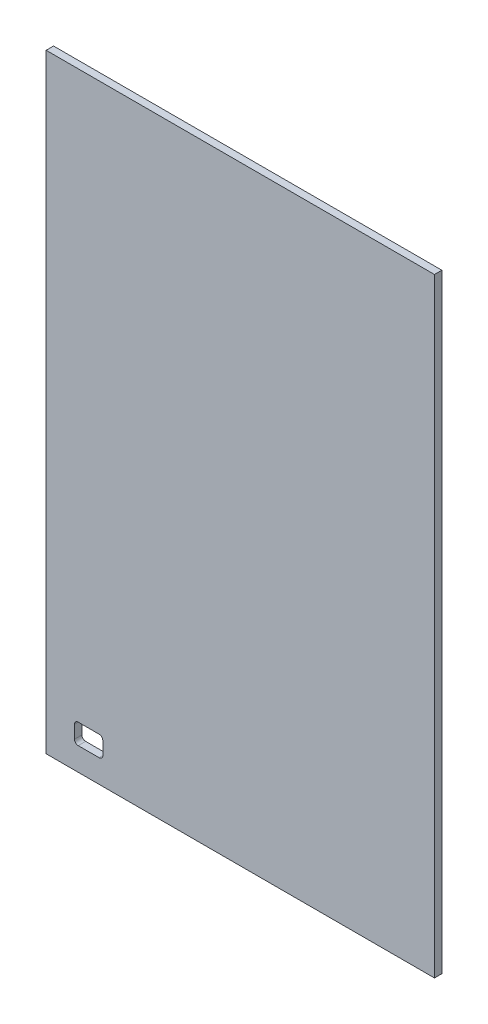
SolidWorks part; units mm, degrees
ref_plane "Front Plane" through (0, 0, 0) normal (0, 0, 1) x (1, 0, 0)
ref_plane "Top Plane" through (0, 0, 0) normal (0, 1, 0) x (1, 0, 0)
ref_plane "Right Plane" through (0, 0, 0) normal (1, 0, 0) x (0, 0, -1)
sketch "Sketch1" plane through (0, 0, 0) normal (0, 0, 1) x (1, 0, 0)
  line L1 (0, 0) -> (420, 0)
  line L2 (0, 0) -> (0, 658.95)
  line L3 (0, 658.95) -> (420, 658.95)
  line L4 (420, 0) -> (420, 658.95)
  line L12 (61.3, 43) -> (61.3, 29) construction
  line L13 (57.3, 25) -> (34.7, 25) construction
  line L14 (30.7, 29) -> (30.7, 43) construction
  line L15 (34.7, 47) -> (57.3, 47) construction
  line L16 (61.3, 43) -> (61.3, 29)
  line L17 (57.3, 25) -> (34.7, 25)
  line L18 (30.7, 29) -> (30.7, 43)
  line L19 (34.7, 47) -> (57.3, 47)
  arc A8 (59.6218, 46.2572) -> (57.3, 47) centre (57.3, 43) ccw construction
  arc A9 (60.6102, 45.2456) -> (59.6218, 46.2572) centre (57.3, 43) ccw construction
  arc A10 (61.3, 43) -> (60.6102, 45.2456) centre (57.3, 43) ccw construction
  arc A11 (60.6102, 26.7544) -> (61.3, 29) centre (57.3, 29) ccw construction
  arc A12 (59.6218, 25.7428) -> (60.6102, 26.7544) centre (57.3, 29) ccw construction
  arc A13 (57.3, 25) -> (59.6218, 25.7428) centre (57.3, 29) ccw construction
  arc A14 (32.3782, 25.7428) -> (34.7, 25) centre (34.7, 29) ccw construction
  arc A15 (31.3898, 26.7544) -> (32.3782, 25.7428) centre (34.7, 29) ccw construction
  arc A16 (30.7, 29) -> (31.3898, 26.7544) centre (34.7, 29) ccw construction
  arc A17 (31.3898, 45.2456) -> (30.7, 43) centre (34.7, 43) ccw construction
  arc A18 (32.3782, 46.2572) -> (31.3898, 45.2456) centre (34.7, 43) ccw construction
  arc A19 (34.7, 47) -> (32.3782, 46.2572) centre (34.7, 43) ccw construction
  arc A20 (59.6218, 46.2572) -> (57.3, 47) centre (57.3, 43) ccw
  arc A21 (60.6102, 45.2456) -> (59.6218, 46.2572) centre (57.3, 43) ccw
  arc A22 (61.3, 43) -> (60.6102, 45.2456) centre (57.3, 43) ccw
  arc A23 (60.6102, 26.7544) -> (61.3, 29) centre (57.3, 29) ccw
  arc A24 (59.6218, 25.7428) -> (60.6102, 26.7544) centre (57.3, 29) ccw
  arc A25 (57.3, 25) -> (59.6218, 25.7428) centre (57.3, 29) ccw
  arc A26 (32.3782, 25.7428) -> (34.7, 25) centre (34.7, 29) ccw
  arc A27 (31.3898, 26.7544) -> (32.3782, 25.7428) centre (34.7, 29) ccw
  arc A28 (30.7, 29) -> (31.3898, 26.7544) centre (34.7, 29) ccw
  arc A29 (31.3898, 45.2456) -> (30.7, 43) centre (34.7, 43) ccw
  arc A30 (32.3782, 46.2572) -> (31.3898, 45.2456) centre (34.7, 43) ccw
  arc A31 (34.7, 47) -> (32.3782, 46.2572) centre (34.7, 43) ccw
  dimension "D1" = 658.95
  dimension "D2" = 420
extrude "Boss-Extrude1" add sketch "Sketch1" along normal blind 8
